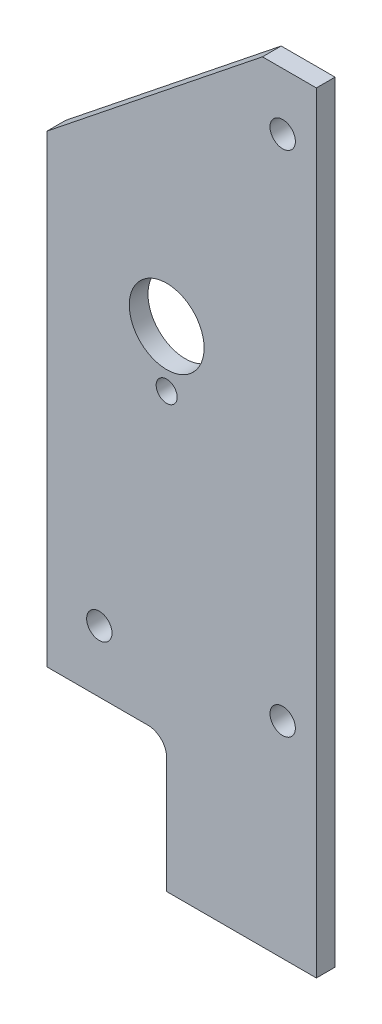
SolidWorks part; units mm, degrees
material "ABS PC"
ref_plane "Front Plane" through (0, 0, 0) normal (0, 0, 1) x (1, 0, 0)
ref_plane "Top Plane" through (0, 0, 0) normal (0, 1, 0) x (1, 0, 0)
ref_plane "Right Plane" through (0, 0, 0) normal (1, 0, 0) x (0, 0, -1)
sketch "Sketch1" plane through (0, 0, 0) normal (0, 0, 1) x (1, 0, 0)
  line L7 (-25.4, 0) -> (0, 0)
  line L8 (0, 0) -> (0, 130.81)
  line L9 (0, 130.81) -> (-9.144, 130.81)
  line L10 (-9.144, 130.81) -> (-45.72, 101.6)
  line L11 (-45.72, 101.6) -> (-45.72, 22.86)
  line L12 (-45.72, 22.86) -> (-28.575, 22.86)
  line L13 (-25.4, 19.685) -> (-25.4, 0)
  line L14 (-25.4, 0) -> (0, 0)
  line L15 (0, 0) -> (0, 130.81)
  line L16 (0, 130.81) -> (-9.144, 130.81)
  line L17 (-9.144, 130.81) -> (-45.72, 101.6)
  line L18 (-45.72, 101.6) -> (-45.72, 22.86)
  line L19 (-45.72, 22.86) -> (-28.575, 22.86)
  line L20 (-25.4, 19.685) -> (-25.4, 0)
  arc A1 (-25.4, 19.685) -> (-28.575, 22.86) centre (-28.575, 19.685) ccw
  arc A2 (-25.4, 19.685) -> (-28.575, 22.86) centre (-28.575, 19.685) ccw
  dimension "D1" = 0
extrude "Boss-Extrude1" add sketch "Sketch1" against normal blind 3.175
hole_wizard "#6 Clearance Hole1" positions "Sketch3" profile "Sketch2" hole size "#6" standard "ANSI Inch" end condition through all
sketch "Sketch3" plane through (0, 0, 0) normal (0, 0, 1) x (1, 0, 0)
  point P0 (-5.715, 34.925)
  point P3 (-36.83, 33.3375)
  point P6 (-5.715, 121.158)
sketch "Sketch2" plane through (-5.715, 34.925, 0) normal (1, 0, 0) x (0, -1, 0)
  line L0 (0, 0) -> (0, 3.175)
  line L1 (0, 3.175) -> (2.1526, 3.175)
  line L2 (2.1526, 3.175) -> (2.1526, 0)
  line L5 (2.1526, 0) -> (0, 0)
  line L11 (0, -6.35) -> (0, 107.95) construction
  dimension "Thru Hole Dia." = 4.3053
  dimension "Thru Hole Depth" = 3.175
hole_wizard "1/2 (0.5) Diameter Hole1" positions "Sketch5" profile "Sketch4" hole size "1/2" standard "ANSI Inch" end condition through all
sketch "Sketch5" plane through (0, 0, 0) normal (0, 0, 1) x (1, 0, 0)
  point P0 (-25.4, 83.058)
sketch "Sketch4" plane through (-25.4, 83.058, 0) normal (1, 0, 0) x (0, -1, 0)
  line L0 (0, 0) -> (0, 3.175)
  line L1 (0, 3.175) -> (6.35, 3.175)
  line L2 (6.35, 3.175) -> (6.35, 0)
  line L5 (6.35, 0) -> (0, 0)
  line L11 (0, -6.35) -> (0, 107.95) construction
  dimension "Thru Hole Dia." = 12.7
  dimension "Thru Hole Depth" = 3.175
hole_wizard "9/64 (0.14063) Diameter Hole1" positions "Sketch7" profile "Sketch6" hole size "9/64" standard "ANSI Inch" end condition through all
sketch "Sketch7" plane through (0, 0, 0) normal (0, 0, 1) x (1, 0, 0)
  point P0 (-25.4, 73.533)
sketch "Sketch6" plane through (-25.4, 73.533, 0) normal (1, 0, 0) x (0, -1, 0)
  line L0 (0, 0) -> (0, 3.175)
  line L1 (0, 3.175) -> (1.786, 3.175)
  line L2 (1.786, 3.175) -> (1.786, 0)
  line L5 (1.786, 0) -> (0, 0)
  line L11 (0, -6.35) -> (0, 107.95) construction
  dimension "Thru Hole Dia." = 3.572
  dimension "Thru Hole Depth" = 3.175
